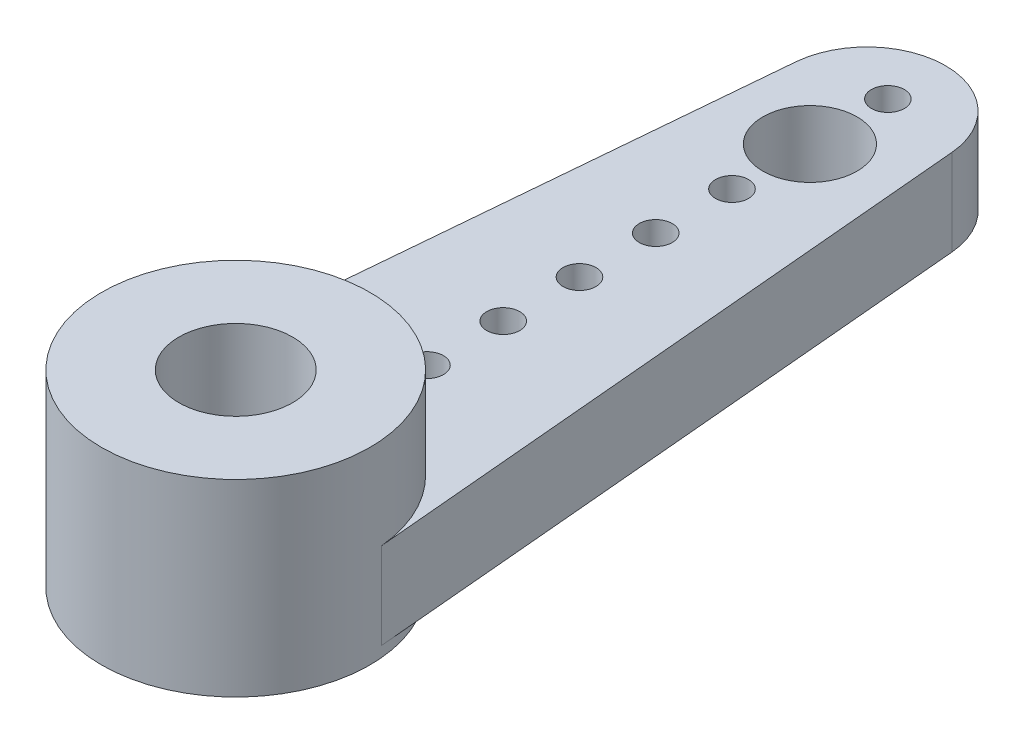
SolidWorks part; units mm, degrees
ref_plane "Front Plane" through (0, 0, 0) normal (0, 0, 1) x (1, 0, 0)
ref_plane "Top Plane" through (0, 0, 0) normal (0, 1, 0) x (1, 0, 0)
ref_plane "Right Plane" through (0, 0, 0) normal (1, 0, 0) x (0, 0, -1)
sketch "Sketch1" plane through (0, 0, 0) normal (0, 1, 0) x (1, 0, 0)
  line L0 (-3.4066, 0.302) -> (-1.9922, 16.2566)
  line L3 (1.9922, 16.2566) -> (3.4066, 0.302)
  line L4 (0, 0) -> (0, 16.08) construction
  line L5 (0, 18.08) -> (0, 16.08) construction
  line L6 (0, 0) -> (0, -3.42) construction
  arc A2 (-3.4066, 0.302) -> (3.4066, 0.302) centre (0, 0) ccw
  arc A3 (1.9922, 16.2566) -> (-1.9922, 16.2566) centre (0, 16.08) ccw
  dimension "D2" = 3.42
  dimension "D3" = 2
  dimension "D1" = 21.5
extrude "Boss-Extrude1" add sketch "Sketch1" along normal blind 2.2
sketch "Sketch2" plane through (0, 2.2, 0) normal (0, 1, 0) x (1, 0, 0)
  circle A0 centre (0, 0) radius 3.42
  arc A1 (-3.4066, 0.302) -> (3.4066, 0.302) centre (0, 0) ccw construction
extrude "Boss-Extrude2" add sketch "Sketch2" along normal blind 2.33
sketch "Sketch3" plane through (0, 4.53, 0) normal (0, 1, 0) x (1, 0, 0)
  circle A0 centre (0, 0) radius 2.06
  circle A1 centre (0, 0) radius 3.42 construction
  dimension "D1" = 1.36
sketch "Sketch4" plane through (0, 0, 0) normal (0, -1, 0) x (1, 0, 0)
  circle A2 centre (0, 0) radius 2.325
  dimension "D1" = 4.65
sketch "Sketch5" plane through (0, 0, 0) normal (0, 1, 0) x (1, 0, 0)
  circle A0 centre (0, 0) radius 1.16
  dimension "D1" = 2.32
sketch "Sketch6" plane through (0, 2.2, 0) normal (0, 1, 0) x (1, 0, 0)
  line L0 (0, 14.08) -> (0, 3.42) construction
  line L1 (0, 3.42) -> (0, -3.42) construction
  line L2 (0, 4.45) -> (2.0836, 4.45) construction
  line L3 (0, 5.29) -> (2.2632, 5.29) construction
  line L4 (0, 16.19) -> (2.6495, 16.19) construction
  line L5 (0.5439, -3.42) -> (4.0041, -3.42) construction
  line L6 (0, 12.64) -> (0, 14.625) construction
  line L7 (0, 16.61) -> (0, 14.625) construction
  line L8 (0, 12.22) -> (1.8481, 12.22) construction
  arc A0 (1.9922, 16.2566) -> (-1.9922, 16.2566) centre (0, 16.08) ccw construction
  arc A1 (3.4066, 0.302) -> (-3.4066, 0.302) centre (0, 0) ccw construction
  circle A2 centre (0, 4.87) radius 0.42
  circle A3 centre (0, 6.8125) radius 0.42
  circle A4 centre (0, 8.755) radius 0.42
  circle A5 centre (0, 10.6975) radius 0.42
  circle A6 centre (0, 12.64) radius 0.42
  circle A7 centre (0, 0) radius 3.42 construction
  arc A10 (-3.4066, 0.302) -> (3.4066, 0.302) centre (0, 0) ccw construction
  circle A11 centre (0, 14.625) radius 0.7
  circle A13 centre (0, 16.61) radius 0.42
  point P27 (0, 5.29)
  point P28 (0, 16.19)
  point P29 (0, 14.625)
  point P31 (0, 5.29)
  dimension "D4" = 19.61
  dimension "D5" = 1.4
  dimension "D6" = 15.64
  dimension "D2" = 7.87
  dimension "D3" = 10.9
  dimension "D1" = 5
extrude "Cut-Extrude5" cut sketch "Sketch6" against normal through all
mirror "Mirror1" [suppressed] about plane through (0, 0, 0) normal (0, 0, 1)
extrude "Cut-Extrude9" [suppressed] cut sketch "Sketch5" along normal through all
extrude "Cut-Extrude10" [suppressed] cut sketch "Sketch4" against normal blind 0.8
extrude "Cut-Extrude11" [suppressed] cut sketch "Sketch3" against normal blind 2.65
sketch "Sketch9" plane through (0, 0, 0) normal (0, -1, 0) x (1, 0, 0)
  circle A0 centre (0, 0) radius 3.42
  arc A1 (3.4066, -0.302) -> (-3.4066, -0.302) centre (0, 0) ccw construction
extrude "Boss-Extrude3" add sketch "Sketch9" along normal offset from surface (0.27 mm away) 4.8
sketch "Sketch10" plane through (0, -0.27, 0) normal (0, -1, 0) x (1, 0, 0)
  circle A0 centre (0, 0) radius 2.29
  dimension "D1" = 4.58
extrude "Cut-Extrude12" cut sketch "Sketch10" against normal blind 0.85
hole_wizard "M2.5 Clearance Hole2" positions "Sketch11" profile "Sketch12" hole size "M2.5" standard "ANSI Metric" end condition through all
sketch "Sketch11" plane through (0, 0.58, 0) normal (0, -1, 0) x (-1, 0, 0)
  point P0 (0, 0)
sketch "Sketch12" plane through (0, 0.58, 0) normal (1, 0, 0) x (0, 0, -1)
  line L0 (0, 0) -> (0, 3.95)
  line L1 (0, 3.95) -> (1.45, 3.95)
  line L2 (1.45, 3.95) -> (1.45, 0)
  line L5 (1.45, 0) -> (0, 0)
  line L11 (0, -6.35) -> (0, 107.95) construction
  dimension "Thru Hole Dia." = 2.9
  dimension "Thru Hole Depth" = 3.95
hole_wizard "M2 Clearance Hole1" positions "Sketch13" profile "Sketch14" hole size "M2" standard "ANSI Metric" end condition through all
sketch "Sketch13" plane through (0, 0, 0) normal (0, -1, 0) x (-1, 0, 0)
  point P0 (0, 14.625)
sketch "Sketch14" plane through (0, 0, -14.625) normal (1, 0, 0) x (0, 0, -1)
  line L0 (0, 0) -> (0, 4.53)
  line L1 (0, 4.53) -> (1.2, 4.53)
  line L2 (1.2, 4.53) -> (1.2, 0)
  line L5 (1.2, 0) -> (0, 0)
  line L11 (0, -6.35) -> (0, 107.95) construction
  dimension "Thru Hole Dia." = 2.4
  dimension "Thru Hole Depth" = 4.53
